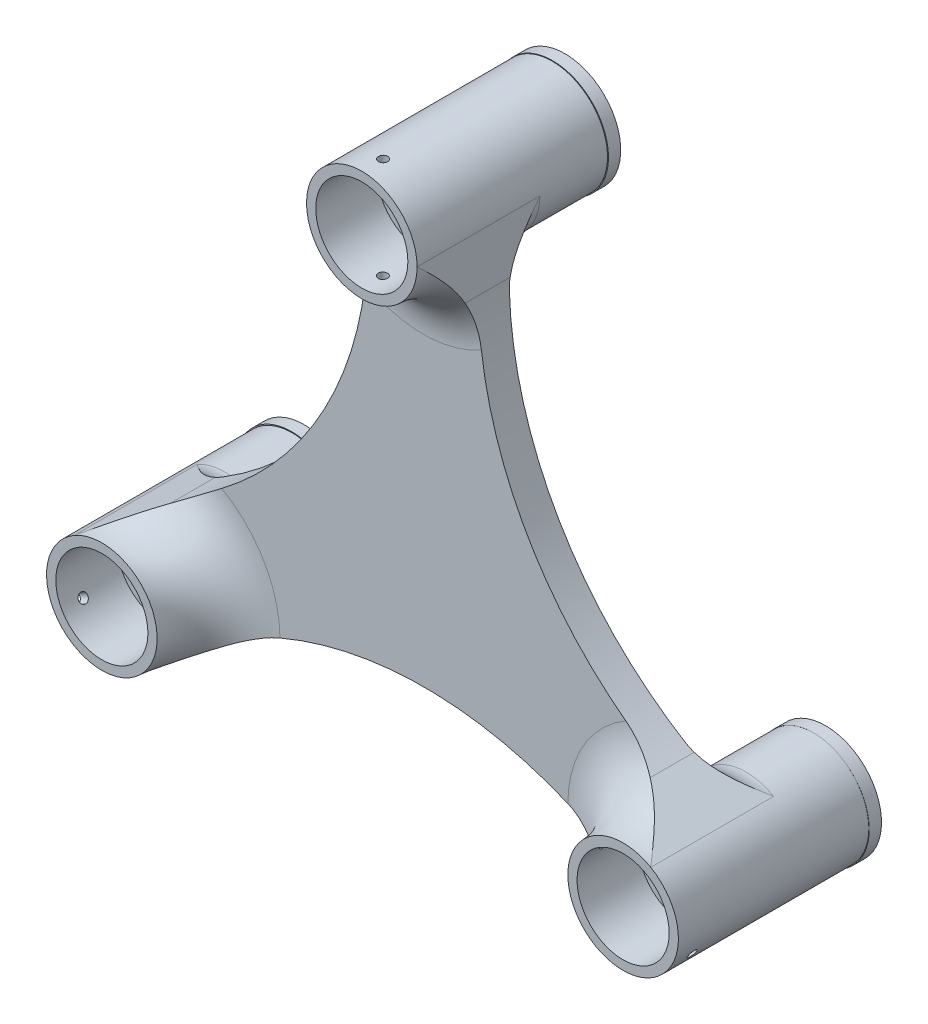
SolidWorks part; units mm, degrees
material "Custom Plastic PLA"
ref_plane "Front Plane" through (0, 0, 0) normal (0, 0, 1) x (1, 0, 0)
ref_plane "Top Plane" through (0, 0, 0) normal (0, 1, 0) x (1, 0, 0)
ref_plane "Right Plane" through (0, 0, 0) normal (1, 0, 0) x (0, 0, -1)
sketch "Sketch1" plane through (0, 0, 0) normal (0, 0, 1) x (1, 0, 0)
  line L6 (-9.0739, 49) -> (8.9261, 49) construction
  line L7 (-9.0739, 49) -> (-9.0739, 39.7091)
  line L8 (8.9261, 49) -> (8.9261, 39.9652)
  line L9 (-0.0041, -0.0024) -> (0.0041, -0.0024)
  line L10 (46.9722, -16.6418) -> (37.9722, -32.2302) construction
  line L11 (46.9722, -16.6418) -> (38.9261, -11.9963)
  line L12 (0, 0.0047) -> (-0.0041, -0.0024)
  line L13 (37.9722, -32.2302) -> (30.1478, -27.7128)
  line L14 (-37.8983, -32.3582) -> (-46.8983, -16.7698) construction
  line L15 (-37.8983, -32.3582) -> (-29.8522, -27.7128)
  line L16 (0.0041, -0.0024) -> (0, 0.0047)
  line L17 (-46.8983, -16.7698) -> (-39.0739, -12.2524)
  line L18 (-0.0739, 40) -> (-0.0739, 54.8454) construction
  circle A0 centre (0, 0) radius 49.0001 construction
  circle A1 centre (-0.0739, 49) radius 7.5
  circle A4 centre (0, 0) radius 22.1602 construction
  circle A5 centre (-0.0739, 49) radius 9
  circle A6 centre (42.4722, -24.436) radius 7.5
  circle A7 centre (42.4722, -24.436) radius 9
  circle A8 centre (-42.3983, -24.564) radius 7.5
  circle A9 centre (-42.3983, -24.564) radius 9
  arc A10 (-29.8522, -27.7128) -> (30.1478, -27.7128) centre (0.1478, -79.6743) cw
  arc A11 (38.9261, -11.9963) -> (8.9261, 39.9652) centre (68.9261, 39.9652) cw
  arc A12 (-39.0739, -12.2524) -> (-9.0739, 39.7091) centre (-69.0739, 39.7091) ccw
  circle A13 centre (-0.0739, 49) radius 3.4844
  circle A14 centre (42.4722, -24.436) radius 3.4844
  circle A15 centre (-42.3983, -24.564) radius 3.4844
  point P12 (0, 0)
  point P16 (0, 0)
  point P30 (0, 0)
  point P43 (0, 0)
  dimension "D1" = 15
  dimension "D3" = 3
  dimension "D4" = 60
  dimension "D5" = 18
  dimension "D6" = 49
  dimension "D2" = 3
  dimension "D7" = 3
extrude "Boss-Extrude3" add sketch "Sketch1" along normal blind 15 and the other way blind 18 contours L10 A7 A6 | L10 A7 A6 | L6 A5 A1 | L6 A5 A1 | L14 A9 A8 | L14 A9 A8 region at (-0.0739, 57.7454, 0) region at (-38.0256, -16.9902, 0) region at (50.046, -20.0633, 0)
extrude "Boss-Extrude4" add sketch "Sketch1<6>" along normal blind 5 contours A12 L17 A9 L15 A10 L13 A7 L11 A11 L8 A5 L7 L16 L9 L12 | A9 | A7 | A5 | A13 | A15 | A14 region at (-0.0739, 38.7578, 0)
sketch "Sketch1<6>" plane through (0, 0, 0) normal (0, 0, 1) x (1, 0, 0) same geometry as "Sketch1"
fillet "Fillet1" radius 10 3 edges at (-0.0739, 40, 5) (34.678, -19.936, 5) (-34.6041, -20.064, 5)
sketch "Sketch3" plane through (0, 0, -18) normal (0, 0, -1) x (-1, 0, 0)
  circle A0 centre (0, 49.0294) radius 9.0796
  circle A1 centre (42.4607, -24.5147) radius 9.0796
  circle A2 centre (-42.4607, -24.5147) radius 9.0796
  circle A3 centre (0, 49.0294) radius 1.5
  circle A4 centre (42.4607, -24.5147) radius 1.5
  circle A5 centre (-42.4607, -24.5147) radius 1.5
  circle A6 centre (0, 0) radius 19.4071 construction
  point P9 (0, 0)
  point P14 (0, 0)
  dimension "D2" = 3
  dimension "D1" = 3
  dimension "D3" = 3
extrude "Boss-Extrude5" add sketch "Sketch3" against normal blind 2
ref_plane "Plane1" through (-0.0739, 58, 15) normal (0, 1, 0) x (1, 0, 0)
sketch "Sketch4" plane through (-0.0739, 58, 15) normal (0, 1, 0) x (1, 0, 0)
  line L0 (-9, 0) -> (9, 0) construction
  circle A0 centre (0, 3.4487) radius 0.75
  point P5 (0, 0)
  dimension "D1" = 1.5
extrude "Cut-Extrude1" cut sketch "Sketch4" against normal blind 18
sketch "Sketch5" plane through (0, 0, 0) normal (0, 0, -1) x (-1, 0, 0)
  circle A0 centre (0, 0) radius 0.5
  dimension "D1" = 1
extrude "Boss-Extrude6" add sketch "Sketch5" along normal blind 2
pattern_circular "CirPattern1" count 3 over 360 about axis through (0, 0, -2) along (0, 0, -1) of "Cut-Extrude1"
fillet "Fillet2" radius 4 3 edges at (49.9722, -24.436, 0) (7.4261, 49, 0) (-34.8983, -24.564, 0)
fillet "Fillet3" radius 4 3 edges at (-49.8983, -24.564, -16) (34.9722, -24.436, -16) (-7.5739, 49, -16)
fillet "Fillet4" radius 5 3 edges at (-34.6041, -20.064, 0) (34.678, -19.936, 0) (-0.0739, 40, 0)
